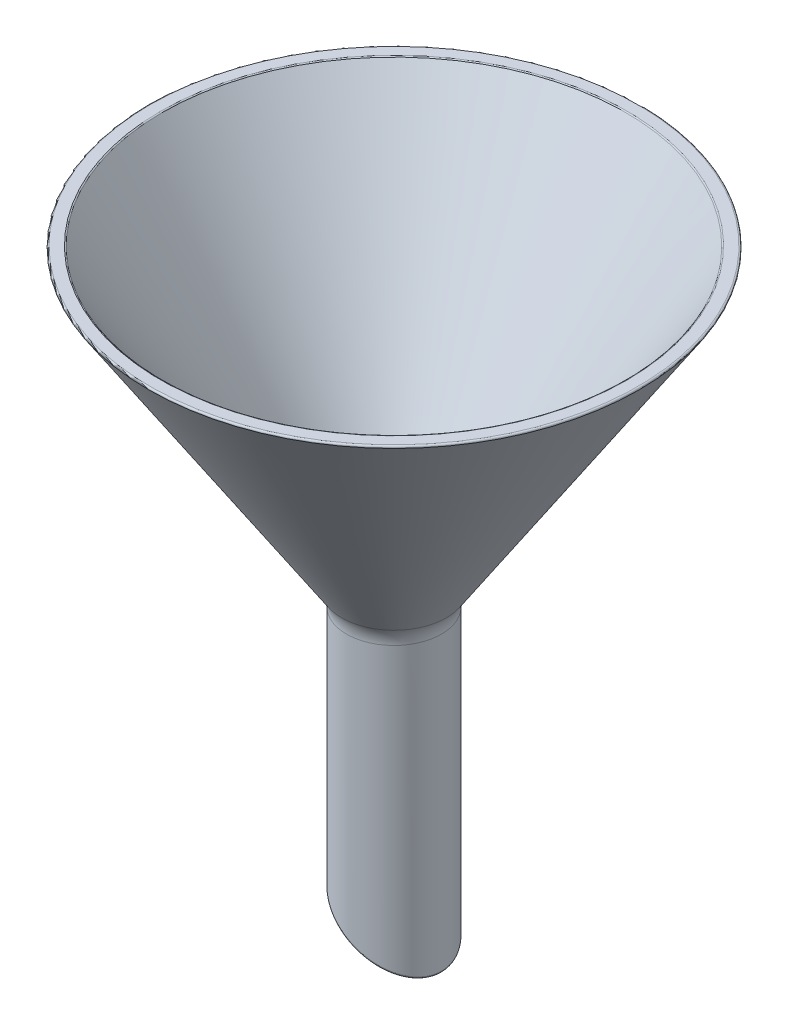
SolidWorks part; units mm, degrees
material "ABS"
ref_plane "Front" through (0, 0, 0) normal (0, 0, 1) x (1, 0, 0)
ref_plane "Top" through (0, 0, 0) normal (0, 1, 0) x (1, 0, 0)
ref_plane "Right" through (0, 0, 0) normal (1, 0, 0) x (0, 0, -1)
sketch "Sketch1" plane through (0, 0, 0) normal (0, 0, 1) x (1, 0, 0)
  line L0 (0, 0) -> (0, -52.07)
  line L1 (0, 0) -> (-20.6375, 0)
  line L2 (-20.6375, 0) -> (-3.9687, -25.4)
  line L3 (-3.9687, -25.4) -> (-3.9687, -52.07)
  line L4 (-3.9687, -52.07) -> (0, -52.07)
  dimension "D1" = 20.6375
  dimension "D2" = 52.07
  dimension "D3" = 26.67
  dimension "D4" = 3.9688
revolve "Revolve1" add sketch "Sketch1" angle 360 about L0
shell "Shell1" thickness 1.016 removed face at (-20.6375, 0, 0)
sketch "Sketch2" plane through (0, 0, 0) normal (0, 0, 1) x (1, 0, 0)
  line L0 (-3.9687, -45.72) -> (3.9688, -50.8)
  line L1 (-3.9687, -25.4) -> (-3.9687, -52.07) construction
  line L2 (3.9688, -52.07) -> (3.9688, -25.4) construction
  line L3 (3.9688, -50.8) -> (3.9688, -52.07)
  line L4 (3.9688, -52.07) -> (-3.9687, -52.07)
  line L5 (-3.9687, -52.07) -> (-3.9687, -45.72)
  dimension "D1" = 1.27
  dimension "D2" = 6.35
extrude "Cut-Extrude1" cut sketch "Sketch2" against normal through all and the other way through all
fillet "Fillet1" radius 2.54 2 edges at (-2.9527, -25.0964, 0) (-3.9687, -25.4, 0)
fillet "Fillet2" radius 0.127 4 edges at (-2.9527, -46.3702, 0) (-3.9687, -45.72, 0) (-19.4223, 0, 0) (-20.6375, 0, 0)
